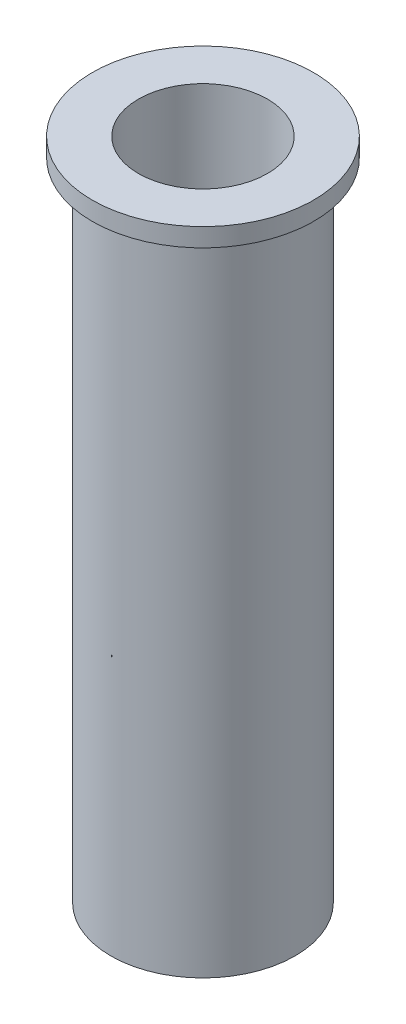
SolidWorks part; units mm, degrees
ref_plane "Front Plane" through (0, 0, 0) normal (0, 0, 1) x (1, 0, 0)
ref_plane "Top Plane" through (0, 0, 0) normal (0, 1, 0) x (1, 0, 0)
ref_plane "Right Plane" through (0, 0, 0) normal (1, 0, 0) x (0, 0, -1)
sketch "Sketch4" plane through (0, 0, 0) normal (0, 1, 0) x (1, 0, 0)
  circle A0 centre (0, 0) radius 10
  dimension "D1" = 20
extrude "Boss-Extrude2" add sketch "Sketch4" along normal blind 70
sketch "Sketch5" plane through (0, 70, 0) normal (0, 1, 0) x (1, 0, 0)
  circle A0 centre (0, 0) radius 12
  dimension "D1" = 24
extrude "Boss-Extrude3" add sketch "Sketch5" along normal blind 2
sketch "Sketch6" plane through (0, 0, 0) normal (0, -1, 0) x (1, 0, 0)
  circle A0 centre (0, 0) radius 7
  dimension "D1" = 14
extrude "Cut-Extrude1" cut sketch "Sketch6" against normal up to next
ref_plane "Plane1" through (0, 0, 0) normal (1, 0, 0) x (0, 0, -1)
sketch "Sketch7" plane through (0, 0, 0) normal (1, 0, 0) x (0, 0, -1)
  line L0 (0, 72) -> (0, 0) construction
  line L1 (7, 72) -> (-7, 72) construction
  line L2 (-10, 35) -> (13.5524, 35) construction
  line L3 (-10, 70) -> (-10, 0) construction
  line L4 (0, 58) -> (0, 48) construction
  line L5 (2, 58) -> (2, 48)
  line L6 (-2, 58) -> (-2, 48)
  line L7 (12, 72) -> (-12, 72) construction
  arc A0 (2, 58) -> (-2, 58) centre (0, 58) ccw
  arc A1 (-2, 48) -> (2, 48) centre (0, 48) ccw
  circle A2 centre (0, 53) radius 2
  circle A3 centre (0, 16) radius 3
  point P11 (0, 53)
  point P18 (0, 60)
  point P19 (0, 46)
  dimension "D1" = 2
  dimension "D5" = 6
  dimension "D2" = 14
  dimension "D3" = 19
  dimension "D4" = 56
extrude "Cut-Extrude3" cut sketch "Sketch7" against normal up to next contours A3 region at (0, 16, 0)
extrude "Cut-Extrude5" cut sketch "Sketch7<4>" along normal blind 1 and the other way through all contours A2 L5 A0 L6 | A2 | A2 L6 A1 L5 region at (0, 57.0708, 0) region at (0, 53, 0) region at (0, 48.9292, 0)
sketch "Sketch7<4>" plane through (0, 0, 0) normal (1, 0, 0) x (0, 0, -1) same geometry as "Sketch7"
